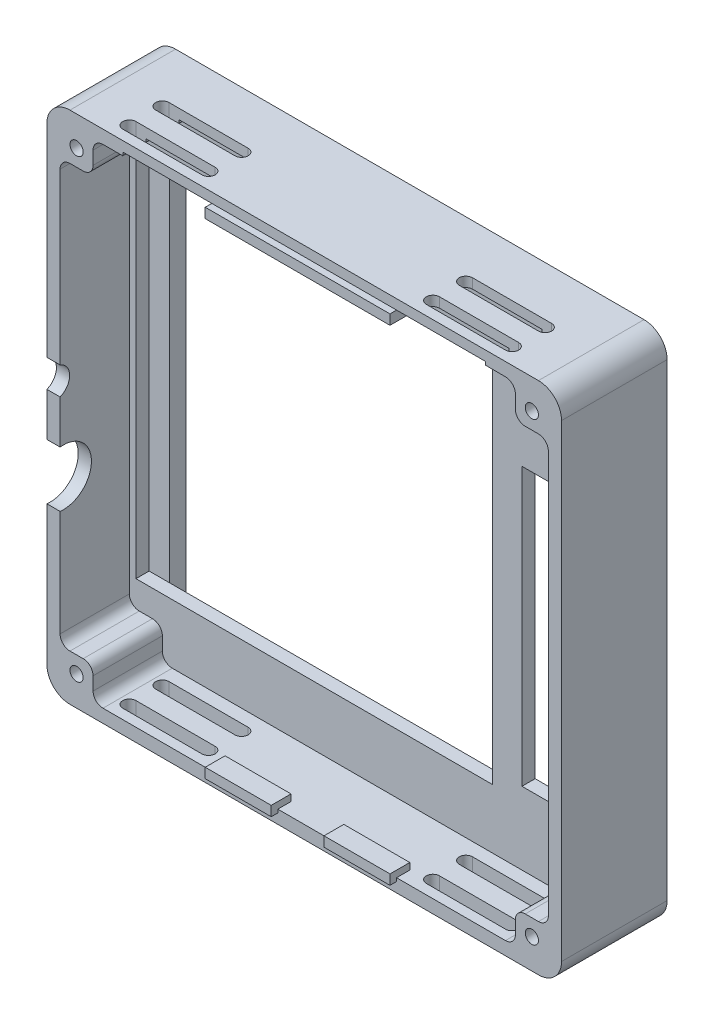
SolidWorks part; units mm, degrees
ref_plane "前视基准面" through (0, 0, 0) normal (0, 0, 1) x (1, 0, 0)
ref_plane "上视基准面" through (0, 0, 0) normal (0, 1, 0) x (1, 0, 0)
ref_plane "右视基准面" through (0, 0, 0) normal (1, 0, 0) x (0, 0, -1)
other "Configuration Table"
sketch "草图1" plane through (0, 0, 0) normal (0, 0, 1) x (1, 0, 0)
  line L1 (-39, -39) -> (39, -39)
  line L2 (-39, -39) -> (-39, 39)
  line L3 (-39, 39) -> (39, 39)
  line L4 (39, -39) -> (39, 39)
  line L5 (-39, -39) -> (39, 39) construction
  line L6 (-39, 39) -> (39, -39) construction
  point P0 (0, 0)
  dimension "D1" = 78
extrude "凸台-拉伸1" add sketch "草图1" along normal blind 5.5
sketch "草图2" plane through (0, 0, 5.5) normal (0, 0, 1) x (1, 0, 0)
  line L1 (-39, -39) -> (39, -39)
  line L2 (-39, -39) -> (-39, 39)
  line L3 (-39, 39) -> (39, 39)
  line L4 (39, -39) -> (39, 39)
  line L5 (-39, -39) -> (39, 39) construction
  line L6 (-39, 39) -> (39, -39) construction
  line L7 (37, 37) -> (-37, 37)
  line L8 (37, 37) -> (37, -37)
  line L9 (37, -37) -> (-37, -37)
  line L10 (-37, 37) -> (-37, -37)
  line L11 (37, 37) -> (-37, -37) construction
  line L12 (37, -37) -> (-37, 37) construction
  line L13 (-37, 37) -> (-32, 37)
  line L14 (-37, 37) -> (-37, 32)
  line L15 (-37, 32) -> (-32, 32)
  line L16 (-32, 37) -> (-32, 32)
  line L17 (37, 37) -> (32, 37)
  line L18 (37, 37) -> (37, 32)
  line L19 (37, 32) -> (32, 32)
  line L20 (32, 37) -> (32, 32)
  line L21 (-37, -37) -> (-32, -37)
  line L22 (-37, -37) -> (-37, -32)
  line L23 (-37, -32) -> (-32, -32)
  line L24 (-32, -37) -> (-32, -32)
  line L25 (37, -37) -> (32, -37)
  line L26 (37, -37) -> (37, -32)
  line L27 (37, -32) -> (32, -32)
  line L28 (32, -37) -> (32, -32)
  point P0 (0, 0)
  point P7 (0, 0)
  line M22 (39, -39) -> (39, 39)
  line M23 (39, 39) -> (-39, 39)
  line M24 (-39, 39) -> (-39, -39)
  line M25 (-39, -39) -> (39, -39)
  dimension "D1" = 2
  dimension "D2" = 5
extrude "凸台-拉伸2" add sketch "草图2" along normal blind 10.5 contours L10 L7 L8 L9 M25 M22 M23 M24 | L16 L7 L10 L15 | L7 L20 L19 L8 | L28 L9 L8 L27 | L9 L24 L23 L10 region at (-37.8969, 0, 5.5) region at (34.5, 34.5, 5.5) region at (-34.5, 34.5, 5.5) region at (34.5, -34.5, 5.5) region at (-34.5, -34.5, 5.5)
fillet "圆角1" radius 1.5 12 edges at (37, 32, 10.75) (32, 32, 10.75) (32, 37, 10.75) (37, -32, 10.75) (32, -32, 10.75) (32, -37, 10.75) (-32, -37, 10.75) (-32, -32, 10.75) (-37, -32, 10.75) (-37, 32, 10.75) (-32, 37, 10.75) (-32, 32, 10.75)
fillet "圆角2" radius 3.5 4 edges at (-39, 39, 8) (39, 39, 8) (39, -39, 8) (-39, -39, 8)
sketch "草图3" plane through (0, 0, 0) normal (0, 0, -1) x (-1, 0, 0)
  line L8 (37.5, -35.5) -> (37.5, 35.5)
  line L9 (-35.5, -37.5) -> (35.5, -37.5)
  line L10 (-37.5, 35.5) -> (-37.5, -35.5)
  line L11 (35.5, 37.5) -> (-35.5, 37.5)
  line L12 (37.5, -35.5) -> (37.5, 35.5)
  line L13 (-35.5, -37.5) -> (35.5, -37.5)
  line L14 (-37.5, 35.5) -> (-37.5, -35.5)
  line L15 (35.5, 37.5) -> (-35.5, 37.5)
  arc A8 (37.5, 35.5) -> (35.5, 37.5) centre (35.5, 35.5) ccw
  arc A9 (35.5, -37.5) -> (37.5, -35.5) centre (35.5, -35.5) ccw
  arc A10 (-37.5, -35.5) -> (-35.5, -37.5) centre (-35.5, -35.5) ccw
  arc A11 (-35.5, 37.5) -> (-37.5, 35.5) centre (-35.5, 35.5) ccw
  arc A12 (37.5, 35.5) -> (35.5, 37.5) centre (35.5, 35.5) ccw
  arc A13 (35.5, -37.5) -> (37.5, -35.5) centre (35.5, -35.5) ccw
  arc A14 (-37.5, -35.5) -> (-35.5, -37.5) centre (-35.5, -35.5) ccw
  arc A15 (-35.5, 37.5) -> (-37.5, 35.5) centre (-35.5, 35.5) ccw
  dimension "D1" = 1.5
extrude "切除-拉伸1" cut sketch "草图3" against normal blind 1
sketch "草图4" plane through (0, 0, 1) normal (0, 0, -1) x (-1, 0, 0)
  line L0 (35.5, 37.5) -> (-35.5, 37.5) construction
  line L1 (-32.95, 37.5) -> (32.95, 37.5)
  line L2 (-32.95, 37.5) -> (-32.95, -33)
  line L3 (-32.95, -33) -> (32.95, -33)
  line L4 (32.95, 37.5) -> (32.95, -33)
  line L6 (0, 0) -> (0, 26.6317) construction
  line L7 (-32.95, 36.85) -> (32.95, 36.85)
  line L8 (27.5, 36.85) -> (27.5, 37.5)
  line L9 (-27.5, 36.85) -> (-27.5, 37.5)
  line M10 (35.5, 37.5) -> (-35.5, 37.5)
  dimension "D1" = 70.5
  dimension "D2" = 65.9
  dimension "D3" = 0.65
  dimension "D4" = 55
extrude "切除-拉伸2" cut sketch "草图4" against normal blind 2.5 contours L3 L6 L7 L2 | L6 L3 L4 L7 | L7 L6 L9 M10 | L6 L7 L8 L1 region at (0, 37.175, 1) region at (30.225, 35.8897, 1)
sketch "草图5" plane through (0, 0, 1) normal (0, 0, -1) x (-1, 0, 0)
  line L0 (-35.5, 39) -> (35.5, 39) construction
  line L1 (-34.5, -34.5) -> (34.5, -34.5) construction
  line L2 (-34.5, -34.5) -> (-34.5, 34.5) construction
  line L3 (-34.5, 34.5) -> (34.5, 34.5) construction
  line L4 (34.5, -34.5) -> (34.5, 34.5) construction
  line L5 (-34.5, -34.5) -> (34.5, 34.5) construction
  line L6 (-34.5, 34.5) -> (34.5, -34.5) construction
  circle A0 centre (-34.5, 34.5) radius 1
  circle A1 centre (34.5, 34.5) radius 1
  circle A2 centre (34.5, -34.5) radius 1
  circle A3 centre (-34.5, -34.5) radius 1
  point P0 (0, 0)
  dimension "D2" = 2
  dimension "D1" = 4.5
extrude "切除-拉伸3" cut sketch "草图5" against normal through all
sketch "草图6" plane through (0, 0, 3.5) normal (0, 0, -1) x (-1, 0, 0)
  line L1 (-27.5, 37.5) -> (27.5, 37.5)
  line L2 (-27.5, 37.5) -> (-27.5, 35.5)
  line L3 (-27.5, 35.5) -> (27.5, 35.5)
  line L4 (27.5, 37.5) -> (27.5, 35.5)
  line L5 (-18, 30) -> (36, 30)
  line L6 (-18, 30) -> (-18, -28)
  line L7 (-18, -28) -> (36, -28)
  line L8 (36, 30) -> (36, -28)
  line L9 (-35, 16) -> (-22.5, 16)
  line L10 (-35, 16) -> (-35, -26)
  line L11 (-35, -26) -> (-22.5, -26)
  line L12 (-22.5, 16) -> (-22.5, -26)
  dimension "D1" = 2
  dimension "D2" = 54
  dimension "D3" = 30
  dimension "D4" = 58
  dimension "D5" = 36
  dimension "D6" = 22.5
  dimension "D7" = 12.5
  dimension "D8" = 42
  dimension "D9" = 16
extrude "切除-拉伸4" cut sketch "草图6" against normal through all
sketch "草图7" plane through (0, 0, 16) normal (0, 0, 1) x (1, 0, 0)
  line L0 (-15.0283, 0) -> (15.498, 0) construction
  line L17 (0, -8.9343) -> (0, 15.7561) construction
  line L20 (35.5, -37.5) -> (-35.5, -37.5) construction
  line L21 (14, -37.5) -> (4, -37.5)
  line L22 (14, -37.5) -> (14, -36)
  line L23 (14, -36) -> (4, -36)
  line L24 (4, -37.5) -> (4, -36)
  line L25 (-27.5, 37.5) -> (27.5, 37.5) construction
  line L26 (-4, -37.5) -> (-14, -37.5)
  line L27 (-4, -37.5) -> (-4, -36)
  line L28 (-4, -36) -> (-14, -36)
  line L29 (-14, -37.5) -> (-14, -36)
  line L30 (-14, 37.5) -> (14, 37.5)
  line L31 (-14, 37.5) -> (-14, 36)
  line L32 (-14, 36) -> (14, 36)
  line L33 (14, 37.5) -> (14, 36)
  dimension "D1" = 1.5
  dimension "D2" = 28
  dimension "D4" = 1.5
  dimension "D5" = 28
  dimension "D6" = 8
extrude "凸台-拉伸3" add sketch "草图7" along normal blind 1 and the other way blind 2
sketch "草图8" plane through (-39, 0, 0) normal (1, 0, 0) x (0, 0, -1)
  line L0 (-16, -35.5) -> (0, -35.5) construction
  line L1 (-16, -35.5) -> (-16, 35.5) construction
  line L2 (-16, 4.8) -> (-16, 0.6) construction
  circle A0 centre (-15.5, -10.2) radius 4.25
  circle A1 centre (-16.8, 2.7) radius 2.2472
  dimension "D1" = 8.5
  dimension "D4" = 4.2
  dimension "D2" = 25.3
  dimension "D3" = 0.5
  dimension "D5" = 38.2
  dimension "D6" = 0.8
extrude "切除-拉伸5" cut sketch "草图8" along normal blind 10
sketch "草图9" plane through (0, -39, 0) normal (0, -1, 0) x (1, 0, 0)
  line L0 (-29, 13.5) -> (-17, 13.5) construction
  line L1 (-29, 14.5) -> (-17, 14.5)
  line L2 (-29, 12.5) -> (-17, 12.5)
  line L3 (-39, 0) -> (-39, 16) construction
  line L4 (-35.5, 16) -> (35.5, 16) construction
  line L5 (-29, 8.5) -> (-17, 8.5) construction
  line L6 (-29, 9.5) -> (-17, 9.5)
  line L7 (-29, 7.5) -> (-17, 7.5)
  line L8 (-29, 13.5) -> (-29, 8.5) construction
  line L9 (0, -1000) -> (0, 49000) construction
  line L11 (29, 8.5) -> (17, 8.5) construction
  line L12 (29, 9.5) -> (17, 9.5)
  line L13 (29, 7.5) -> (17, 7.5)
  line L14 (29, 13.5) -> (17, 13.5) construction
  line L15 (29, 14.5) -> (17, 14.5)
  line L16 (29, 12.5) -> (17, 12.5)
  arc A0 (-29, 14.5) -> (-29, 12.5) centre (-29, 13.5) ccw
  arc A1 (-17, 12.5) -> (-17, 14.5) centre (-17, 13.5) ccw
  arc A2 (-29, 9.5) -> (-29, 7.5) centre (-29, 8.5) ccw
  arc A3 (-17, 7.5) -> (-17, 9.5) centre (-17, 8.5) ccw
  arc A4 (29, 9.5) -> (29, 7.5) centre (29, 8.5) cw
  arc A5 (17, 7.5) -> (17, 9.5) centre (17, 8.5) cw
  arc A6 (29, 14.5) -> (29, 12.5) centre (29, 13.5) cw
  arc A7 (17, 12.5) -> (17, 14.5) centre (17, 13.5) cw
  point P2 (-23, 13.5)
  point P15 (-23, 8.5)
  point P27 (23, 8.5)
  point P34 (23, 13.5)
  dimension "D3" = 1
  dimension "D1" = 12
  dimension "D2" = 10
  dimension "D4" = 2.5
  dimension "D6" = 5
  dimension "D5" = 2
extrude "切除-拉伸6" cut sketch "草图9" against normal through all
